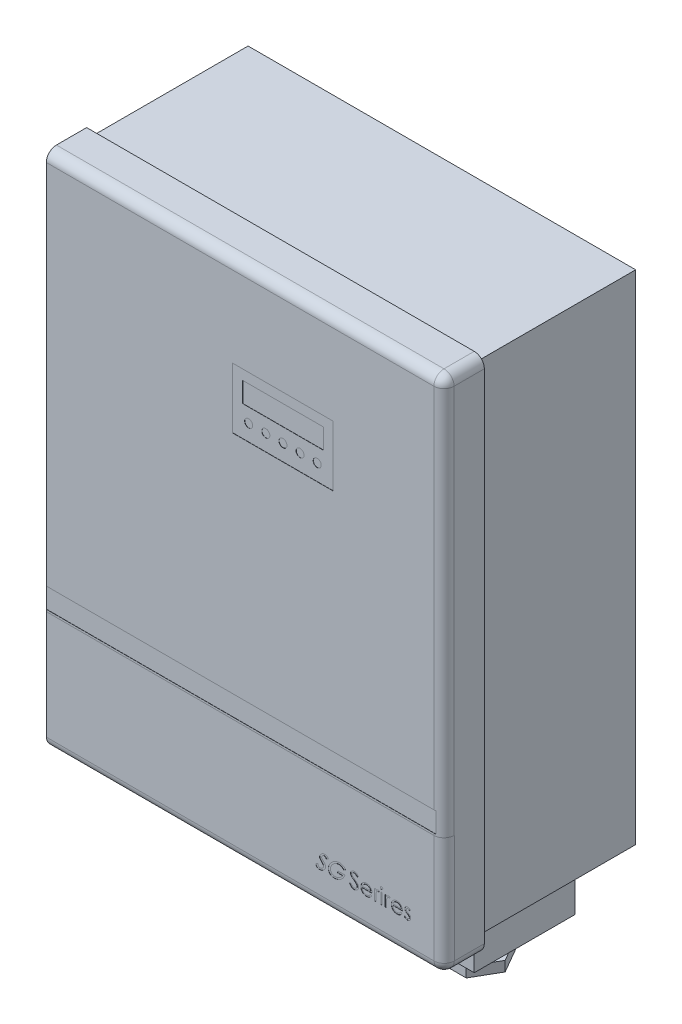
SolidWorks part; units mm, degrees
ref_plane "Alzado" through (0, 0, 0) normal (0, 0, 1) x (1, 0, 0)
ref_plane "Planta" through (0, 0, 0) normal (0, 1, 0) x (1, 0, 0)
ref_plane "Vista lateral" through (0, 0, 0) normal (1, 0, 0) x (0, 0, -1)
sketch "Croquis1" plane through (0, 0, 0) normal (0, 0, 1) x (1, 0, 0)
  line L1 (-323.85, 313.69) -> (323.85, 313.69)
  line L2 (-323.85, 313.69) -> (-323.85, -313.69)
  line L3 (-323.85, -313.69) -> (323.85, -313.69)
  line L4 (323.85, 313.69) -> (323.85, -313.69)
  line L5 (-323.85, 313.69) -> (323.85, -313.69) construction
  line L6 (-323.85, -313.69) -> (323.85, 313.69) construction
  line L7 (-311.15, -300.99) -> (311.15, -300.99)
  line L8 (-311.15, -300.99) -> (-311.15, 300.99)
  line L9 (-311.15, 300.99) -> (311.15, 300.99)
  line L10 (311.15, -300.99) -> (311.15, 300.99)
  line L11 (-311.15, -300.99) -> (311.15, 300.99) construction
  line L12 (-311.15, 300.99) -> (311.15, -300.99) construction
  point P0 (0, 0)
  point P6 (0, 0)
  point P11 (-311.15, 300.99)
  dimension "D1" = 647.7
  dimension "D2" = 627.38
  dimension "D3" = 12.7
  dimension "D4" = 12.7
extrude "Saliente-Extruir1" add sketch "Croquis1" along normal blind 203.2
sketch "Croquis2" plane through (0, 0, 203.2) normal (0, 0, 1) x (1, 0, 0)
  line L0 (323.85, -313.69) -> (323.85, 313.69) construction
  line L1 (-336.55, -326.39) -> (336.55, -326.39)
  line L2 (-336.55, -326.39) -> (-336.55, 326.39)
  line L3 (-336.55, 326.39) -> (336.55, 326.39)
  line L4 (336.55, -326.39) -> (336.55, 326.39)
  line L5 (-336.55, -326.39) -> (336.55, 326.39) construction
  line L6 (-336.55, 326.39) -> (336.55, -326.39) construction
  line L7 (323.85, 313.69) -> (-323.85, 313.69) construction
  point P0 (0, 0)
  dimension "D1" = 12.7
  dimension "D2" = 12.7
extrude "Saliente-Extruir2" add sketch "Croquis2" along normal blind 50.8
sketch "Croquis3" plane through (0, 0, 254) normal (0, 0, 1) x (1, 0, 0)
  line L0 (336.55, -326.39) -> (336.55, 326.39) construction
  line L1 (-336.55, -148.59) -> (336.55, -148.59)
  line L2 (-336.55, -148.59) -> (-336.55, -173.99)
  line L3 (-336.55, -173.99) -> (336.55, -173.99)
  line L4 (336.55, -148.59) -> (336.55, -173.99)
  line L5 (-336.55, -148.59) -> (336.55, -173.99) construction
  line L6 (-336.55, -173.99) -> (336.55, -148.59) construction
  point P0 (336.55, -161.29)
  dimension "D1" = 25.4
  dimension "D2" = 673.1
  dimension "D3" = 165.1
extrude "Cortar-Extruir1" cut sketch "Croquis3" against normal blind 0.254
sketch "Croquis5" plane through (0, 0, 254) normal (0, 0, 1) x (1, 0, 0)
  line L0 (-336.55, -173.99) -> (-336.55, -326.39) construction
  line L1 (-336.55, -176.53) -> (336.55, -176.53)
  line L2 (-336.55, -176.53) -> (-336.55, -326.39)
  line L3 (-336.55, -326.39) -> (336.55, -326.39)
  line L4 (336.55, -176.53) -> (336.55, -326.39)
  line L5 (-336.55, -173.99) -> (336.55, -173.99) construction
  dimension "D1" = 2.54
extrude "Cortar-Extruir2" cut sketch "Croquis5" against normal blind 0.254
fillet "Redondeo1" radius 12.7 4 edges at (336.55, 326.39, 228.6) (336.55, -326.39, 228.473) (-336.55, -326.39, 228.473) (-336.55, 326.39, 228.6)
fillet "Redondeo4" radius 12.7 5 edges at (-336.55, -245.11, 253.746) (-332.8303, -322.6703, 253.746) (336.55, -245.11, 253.746) (332.8303, -322.6703, 253.746) (0, -326.39, 253.746)
fillet "Redondeo5" radius 12.7 5 edges at (336.55, 82.55, 254) (332.8303, 322.6703, 254) (0, 326.39, 254) (-332.8303, 322.6703, 254) (-336.55, 82.55, 254)
sketch "Croquis6" plane through (0, 0, 254) normal (0, 0, 1) x (1, 0, 0)
  line L0 (323.85, -148.59) -> (323.85, 313.69) construction
  line L1 (69.85, 212.09) -> (196.85, 212.09)
  line L2 (69.85, 212.09) -> (69.85, 135.89)
  line L3 (69.85, 135.89) -> (196.85, 135.89)
  line L4 (196.85, 212.09) -> (196.85, 135.89)
  line L5 (323.85, 313.69) -> (-323.85, 313.69) construction
  dimension "D1" = 76.2
  dimension "D2" = 127
  dimension "D3" = 127
  dimension "D4" = 101.6
extrude "Cortar-Extruir3" cut sketch "Croquis6" against normal blind 0.254
sketch "Croquis7" plane through (0, 0, 253.746) normal (0, 0, 1) x (1, 0, 0)
  line L0 (196.85, 212.09) -> (69.85, 212.09) construction
  line L1 (82.55, 173.99) -> (184.15, 173.99)
  line L2 (82.55, 173.99) -> (82.55, 199.39)
  line L3 (82.55, 199.39) -> (184.15, 199.39)
  line L4 (184.15, 173.99) -> (184.15, 199.39)
  line L5 (82.55, 173.99) -> (184.15, 199.39) construction
  line L6 (82.55, 199.39) -> (184.15, 173.99) construction
  line L7 (196.85, 135.89) -> (196.85, 212.09) construction
  line L8 (69.85, 212.09) -> (69.85, 135.89) construction
  point P0 (133.35, 186.69)
  dimension "D1" = 12.7
  dimension "D2" = 12.7
  dimension "D3" = 12.7
  dimension "D4" = 25.4
extrude "Cortar-Extruir4" cut sketch "Croquis7" against normal blind 0.254
sketch "Croquis8" plane through (0, 0, 253.746) normal (0, 0, 1) x (1, 0, 0)
  line L0 (69.85, 135.89) -> (196.85, 135.89) construction
  line L1 (69.85, 212.09) -> (69.85, 135.89) construction
  line L2 (196.85, 135.89) -> (196.85, 212.09) construction
  circle A0 centre (90.17, 156.21) radius 5.08
  circle A1 centre (111.76, 156.21) radius 5.08
  circle A2 centre (133.35, 156.21) radius 5.08
  circle A3 centre (154.94, 156.21) radius 5.08
  circle A4 centre (176.53, 156.21) radius 5.08
  dimension "D1" = 10.16
  dimension "D5" = 20.32
  dimension "D2" = 20.32
  dimension "D3" = 20.32
  dimension "D4" = 5
extrude "Cortar-Extruir5" cut sketch "Croquis8" against normal blind 0.254
sketch "Croquis9" plane through (0, -313.69, 0) normal (0, -1, 0) x (1, 0, 0)
  line L0 (-323.85, 203.2) -> (-323.85, 0) construction
  line L1 (-323.85, 0) -> (323.85, 0) construction
  circle A0 centre (-260.35, 114.3) radius 38.1
  dimension "D1" = 76.2
  dimension "D2" = 63.5
  dimension "D3" = 114.3
extrude "Saliente-Extruir3" add sketch "Croquis9" along normal blind 12.7
sketch "Croquis10" plane through (0, -326.39, 0) normal (0, -1, 0) x (1, 0, 0)
  line L2 (-287.0835, 117.869) -> (-264.795, 126.1967)
  line L3 (-287.0835, 110.731) -> (-264.795, 102.4033)
  line L4 (-255.905, 126.1967) -> (-233.6165, 117.869)
  line L5 (-255.905, 102.4033) -> (-233.6165, 110.731)
  arc A0 (-287.0835, 117.869) -> (-287.0835, 110.731) centre (-285.75, 114.3) ccw
  arc A1 (-233.6165, 110.731) -> (-233.6165, 117.869) centre (-234.95, 114.3) ccw
  arc A2 (-264.795, 102.4033) -> (-255.905, 102.4033) centre (-260.35, 114.3) ccw
  arc A3 (-255.905, 126.1967) -> (-264.795, 126.1967) centre (-260.35, 114.3) ccw
  dimension "D1" = 7.62
  dimension "D2" = 7.62
  dimension "D5" = 25.4
extrude "Saliente-Extruir4" add sketch "Croquis10" along normal blind 25.4
sketch "Croquis11" plane through (0, -313.69, 0) normal (0, -1, 0) x (1, 0, 0)
  line L0 (-38.0669, 140.6157) -> (-38.0669, 149.86)
  line L1 (-38.0669, 129.54) -> (-33.02, 129.54)
  line L2 (-38.0669, 129.54) -> (-38.0669, 138.7843)
  line L3 (-38.0669, 149.86) -> (-33.02, 149.86)
  line L4 (-17.7469, 129.54) -> (-17.7469, 129.5649)
  line L5 (-17.7469, 149.8351) -> (-17.7469, 149.86)
  line L8 (-17.78, 149.86) -> (-17.7469, 149.86)
  line L9 (-17.78, 129.54) -> (-17.7469, 129.54)
  line L10 (0.0331, 129.54) -> (5.08, 129.54)
  line L11 (20.32, 129.54) -> (20.3531, 129.54)
  line L12 (20.3531, 129.54) -> (20.3531, 129.5649)
  line L13 (20.3531, 149.8351) -> (20.3531, 149.86)
  line L14 (20.32, 149.86) -> (20.3531, 149.86)
  line L15 (0.0331, 149.86) -> (5.08, 149.86)
  line L16 (0.0331, 140.6157) -> (0.0331, 149.86)
  line L17 (0.0331, 129.54) -> (0.0331, 138.7843)
  line L18 (0.0331, 91.44) -> (5.08, 91.44)
  line L19 (20.32, 91.44) -> (20.3531, 91.44)
  line L20 (20.3531, 91.44) -> (20.3531, 91.4649)
  line L21 (20.3531, 111.7351) -> (20.3531, 111.76)
  line L22 (20.32, 111.76) -> (20.3531, 111.76)
  line L23 (0.0331, 111.76) -> (5.08, 111.76)
  line L24 (0.0331, 102.5157) -> (0.0331, 111.76)
  line L25 (0.0331, 91.44) -> (0.0331, 100.6843)
  line L26 (0.0331, 53.34) -> (5.08, 53.34)
  line L27 (20.32, 53.34) -> (20.3531, 53.34)
  line L28 (20.3531, 53.34) -> (20.3531, 53.3649)
  line L29 (20.3531, 73.6351) -> (20.3531, 73.66)
  line L30 (20.32, 73.66) -> (20.3531, 73.66)
  line L31 (0.0331, 73.66) -> (5.08, 73.66)
  line L32 (0.0331, 64.4157) -> (0.0331, 73.66)
  line L33 (0.0331, 53.34) -> (0.0331, 62.5843)
  line L34 (-38.0669, 91.44) -> (-33.02, 91.44)
  line L35 (-17.78, 91.44) -> (-17.7469, 91.44)
  line L36 (-17.7469, 91.44) -> (-17.7469, 91.4649)
  line L37 (-17.7469, 111.7351) -> (-17.7469, 111.76)
  line L38 (-17.78, 111.76) -> (-17.7469, 111.76)
  line L39 (-38.0669, 111.76) -> (-33.02, 111.76)
  line L40 (-38.0669, 102.5157) -> (-38.0669, 111.76)
  line L41 (-38.0669, 91.44) -> (-38.0669, 100.6843)
  line L42 (-38.0669, 53.34) -> (-33.02, 53.34)
  line L43 (-17.78, 53.34) -> (-17.7469, 53.34)
  line L44 (-17.7469, 53.34) -> (-17.7469, 53.3649)
  line L45 (-17.7469, 73.6351) -> (-17.7469, 73.66)
  line L46 (-17.78, 73.66) -> (-17.7469, 73.66)
  line L47 (-38.0669, 73.66) -> (-33.02, 73.66)
  line L48 (-38.0669, 64.4157) -> (-38.0669, 73.66)
  line L49 (-38.0669, 53.34) -> (-38.0669, 62.5843)
  line L50 (-323.85, 203.2) -> (323.85, 203.2) construction
  line L51 (-323.85, 0) -> (323.85, 0) construction
  line L52 (-323.85, 203.2) -> (-323.85, 0) construction
  arc A0 (-38.0669, 140.6157) -> (-38.0669, 138.7843) centre (-25.4, 139.7) ccw
  arc A1 (-33.02, 129.54) -> (-17.78, 129.54) centre (-25.4, 139.7) ccw
  arc A2 (-17.7469, 129.5649) -> (-17.7469, 149.8351) centre (-25.4, 139.7) ccw
  arc A3 (-17.78, 149.86) -> (-33.02, 149.86) centre (-25.4, 139.7) ccw
  arc A4 (5.08, 129.54) -> (20.32, 129.54) centre (12.7, 139.7) ccw
  arc A5 (20.3531, 129.5649) -> (20.3531, 149.8351) centre (12.7, 139.7) ccw
  arc A6 (20.32, 149.86) -> (5.08, 149.86) centre (12.7, 139.7) ccw
  arc A7 (0.0331, 140.6157) -> (0.0331, 138.7843) centre (12.7, 139.7) ccw
  arc A8 (5.08, 91.44) -> (20.32, 91.44) centre (12.7, 101.6) ccw
  arc A9 (20.3531, 91.4649) -> (20.3531, 111.7351) centre (12.7, 101.6) ccw
  arc A10 (20.32, 111.76) -> (5.08, 111.76) centre (12.7, 101.6) ccw
  arc A11 (0.0331, 102.5157) -> (0.0331, 100.6843) centre (12.7, 101.6) ccw
  arc A12 (5.08, 53.34) -> (20.32, 53.34) centre (12.7, 63.5) ccw
  arc A13 (20.3531, 53.3649) -> (20.3531, 73.6351) centre (12.7, 63.5) ccw
  arc A14 (20.32, 73.66) -> (5.08, 73.66) centre (12.7, 63.5) ccw
  arc A15 (0.0331, 64.4157) -> (0.0331, 62.5843) centre (12.7, 63.5) ccw
  arc A16 (-33.02, 91.44) -> (-17.78, 91.44) centre (-25.4, 101.6) ccw
  arc A17 (-17.7469, 91.4649) -> (-17.7469, 111.7351) centre (-25.4, 101.6) ccw
  arc A18 (-17.78, 111.76) -> (-33.02, 111.76) centre (-25.4, 101.6) ccw
  arc A19 (-38.0669, 102.5157) -> (-38.0669, 100.6843) centre (-25.4, 101.6) ccw
  arc A20 (-33.02, 53.34) -> (-17.78, 53.34) centre (-25.4, 63.5) ccw
  arc A21 (-17.7469, 53.3649) -> (-17.7469, 73.6351) centre (-25.4, 63.5) ccw
  arc A22 (-17.78, 73.66) -> (-33.02, 73.66) centre (-25.4, 63.5) ccw
  arc A23 (-38.0669, 64.4157) -> (-38.0669, 62.5843) centre (-25.4, 63.5) ccw
  dimension "D1" = 25.4
  dimension "D2" = 20.32
  dimension "D3" = 20.32
  dimension "D6" = 63.5
  dimension "D7" = 63.5
  dimension "D8" = 203.2
  dimension "D4" = 2
  dimension "D5" = 3
extrude "Saliente-Extruir5" add sketch "Croquis11" along normal blind 50.8
sketch "Croquis12" plane through (0, -313.69, 0) normal (0, -1, 0) x (-1, 0, 0)
  line L0 (323.85, -203.2) -> (-323.85, -203.2) construction
  line L1 (323.85, -203.2) -> (323.85, 0) construction
  line L2 (-64.5291, -127.001) -> (-76.044, -127.001)
  line L3 (-64.5291, -127.001) -> (-64.5291, -134.692)
  line L4 (-64.5291, -147.321) -> (-66.0407, -147.321)
  line L5 (-84.8491, -127.001) -> (-84.8491, -130.4004)
  line L6 (-102.6291, -144.708) -> (-102.6291, -147.321)
  line L8 (-64.5291, -144.708) -> (-64.5291, -147.321)
  line L9 (-86.3593, -147.321) -> (-84.8491, -147.321)
  line L10 (-84.8491, -148.9996) -> (-84.8491, -147.321)
  line L11 (-76.356, -127.001) -> (-84.8491, -127.001)
  line L12 (-102.6291, -147.321) -> (-104.1407, -147.321)
  line L13 (-124.4593, -147.321) -> (-122.9491, -147.321)
  line L14 (-122.9491, -148.9996) -> (-122.9491, -147.321)
  line L15 (-122.9491, -127.001) -> (-122.9491, -130.4004)
  line L16 (-114.456, -127.001) -> (-122.9491, -127.001)
  line L17 (-102.6291, -127.001) -> (-114.144, -127.001)
  line L18 (-102.6291, -127.001) -> (-102.6291, -134.692)
  line L19 (-102.6291, -106.608) -> (-102.6291, -109.221)
  line L20 (-102.6291, -109.221) -> (-104.1407, -109.221)
  line L21 (-124.4593, -109.221) -> (-122.9491, -109.221)
  line L22 (-122.9491, -110.8996) -> (-122.9491, -109.221)
  line L23 (-122.9491, -88.901) -> (-122.9491, -92.3004)
  line L24 (-114.456, -88.901) -> (-122.9491, -88.901)
  line L25 (-102.6291, -88.901) -> (-114.144, -88.901)
  line L26 (-102.6291, -88.901) -> (-102.6291, -96.592)
  line L27 (-102.6291, -68.508) -> (-102.6291, -71.121)
  line L28 (-102.6291, -71.121) -> (-104.1407, -71.121)
  line L29 (-124.4593, -71.121) -> (-122.9491, -71.121)
  line L30 (-122.9491, -72.7996) -> (-122.9491, -71.121)
  line L31 (-122.9491, -50.801) -> (-122.9491, -54.2004)
  line L32 (-114.456, -50.801) -> (-122.9491, -50.801)
  line L33 (-102.6291, -50.801) -> (-114.144, -50.801)
  line L34 (-102.6291, -50.801) -> (-102.6291, -58.492)
  line L35 (-64.5291, -106.608) -> (-64.5291, -109.221)
  line L36 (-64.5291, -109.221) -> (-66.0407, -109.221)
  line L37 (-86.3593, -109.221) -> (-84.8491, -109.221)
  line L38 (-84.8491, -110.8996) -> (-84.8491, -109.221)
  line L39 (-84.8491, -88.901) -> (-84.8491, -92.3004)
  line L40 (-76.356, -88.901) -> (-84.8491, -88.901)
  line L41 (-64.5291, -88.901) -> (-76.044, -88.901)
  line L42 (-64.5291, -88.901) -> (-64.5291, -96.592)
  line L43 (-64.5291, -68.508) -> (-64.5291, -71.121)
  line L44 (-64.5291, -71.121) -> (-66.0407, -71.121)
  line L45 (-86.3593, -71.121) -> (-84.8491, -71.121)
  line L46 (-84.8491, -72.7996) -> (-84.8491, -71.121)
  line L47 (-84.8491, -50.801) -> (-84.8491, -54.2004)
  line L48 (-76.356, -50.801) -> (-84.8491, -50.801)
  line L49 (-64.5291, -50.801) -> (-76.044, -50.801)
  line L50 (-64.5291, -50.801) -> (-64.5291, -58.492)
  arc A0 (-64.5291, -144.708) -> (-64.5291, -134.692) centre (-76.2, -139.7) ccw
  arc A1 (-86.3593, -147.321) -> (-66.0407, -147.321) centre (-76.2, -139.7) ccw
  arc A2 (-76.044, -127.001) -> (-76.356, -127.001) centre (-76.2, -139.7) ccw
  arc A3 (-84.8491, -130.4004) -> (-84.8491, -148.9996) centre (-76.2, -139.7) ccw
  arc A4 (-124.4593, -147.321) -> (-104.1407, -147.321) centre (-114.3, -139.7) ccw
  arc A5 (-122.9491, -130.4004) -> (-122.9491, -148.9996) centre (-114.3, -139.7) ccw
  arc A6 (-114.144, -127.001) -> (-114.456, -127.001) centre (-114.3, -139.7) ccw
  arc A7 (-102.6291, -144.708) -> (-102.6291, -134.692) centre (-114.3, -139.7) ccw
  arc A8 (-124.4593, -109.221) -> (-104.1407, -109.221) centre (-114.3, -101.6) ccw
  arc A9 (-122.9491, -92.3004) -> (-122.9491, -110.8996) centre (-114.3, -101.6) ccw
  arc A10 (-114.144, -88.901) -> (-114.456, -88.901) centre (-114.3, -101.6) ccw
  arc A11 (-102.6291, -106.608) -> (-102.6291, -96.592) centre (-114.3, -101.6) ccw
  arc A12 (-124.4593, -71.121) -> (-104.1407, -71.121) centre (-114.3, -63.5) ccw
  arc A13 (-122.9491, -54.2004) -> (-122.9491, -72.7996) centre (-114.3, -63.5) ccw
  arc A14 (-114.144, -50.801) -> (-114.456, -50.801) centre (-114.3, -63.5) ccw
  arc A15 (-102.6291, -68.508) -> (-102.6291, -58.492) centre (-114.3, -63.5) ccw
  arc A16 (-86.3593, -109.221) -> (-66.0407, -109.221) centre (-76.2, -101.6) ccw
  arc A17 (-84.8491, -92.3004) -> (-84.8491, -110.8996) centre (-76.2, -101.6) ccw
  arc A18 (-76.044, -88.901) -> (-76.356, -88.901) centre (-76.2, -101.6) ccw
  arc A19 (-64.5291, -106.608) -> (-64.5291, -96.592) centre (-76.2, -101.6) ccw
  arc A20 (-86.3593, -71.121) -> (-66.0407, -71.121) centre (-76.2, -63.5) ccw
  arc A21 (-84.8491, -54.2004) -> (-84.8491, -72.7996) centre (-76.2, -63.5) ccw
  arc A22 (-76.044, -50.801) -> (-76.356, -50.801) centre (-76.2, -63.5) ccw
  arc A23 (-64.5291, -68.508) -> (-64.5291, -58.492) centre (-76.2, -63.5) ccw
  dimension "D1" = 25.4
  dimension "D2" = 63.5
  dimension "D3" = 20.32
  dimension "D4" = 20.32
  dimension "D5" = 304.8
  dimension "D6" = 2
  dimension "D7" = 3
extrude "Saliente-Extruir7" add sketch "Croquis12" along normal blind 38.1 rebuild error yes
sketch "Croquis13" plane through (0, -313.69, 0) normal (0, -1, 0) x (1, 0, 0)
  line L0 (-323.85, 203.2) -> (323.85, 203.2) construction
  line L1 (90.4291, 165.1) -> (285.75, 165.1)
  line L2 (90.4291, 165.1) -> (90.4291, 38.1)
  line L3 (90.4291, 38.1) -> (285.75, 38.1)
  line L4 (285.75, 165.1) -> (285.75, 38.1)
  line L5 (-323.85, 0) -> (323.85, 0) construction
  line L6 (323.85, 203.2) -> (323.85, 0) construction
  dimension "D1" = 38.1
  dimension "D2" = 38.1
  dimension "D3" = 38.1
extrude "Saliente-Extruir8" add sketch "Croquis13" along normal blind 76.2
sketch "Croquis14" plane through (0, -389.89, 0) normal (0, -1, 0) x (1, 0, 0)
  line L0 (285.75, 165.1) -> (90.4291, 165.1) construction
  line L1 (90.4291, 165.1) -> (164.8775, 165.1)
  line L2 (90.4291, 165.1) -> (90.4291, 38.1)
  line L3 (90.4291, 38.1) -> (164.8775, 38.1)
  line L4 (164.8775, 165.1) -> (164.8775, 38.1)
  line L5 (90.4291, 165.1) -> (90.4291, 38.1) construction
  line L6 (90.4291, 38.1) -> (285.75, 38.1) construction
extrude "Cortar-Extruir6" cut sketch "Croquis14" against normal blind 25.4
fillet "Redondeo9" radius 25.4 1 edges at (164.8775, -364.49, 101.6)
sketch "Croquis15" plane through (0, -389.89, 0) normal (0, -1, 0) x (1, 0, 0)
  line L0 (285.75, 165.1) -> (164.8775, 165.1) construction
  line L1 (261.2139, 101.6) -> (243.2559, 132.7041)
  line L2 (243.2559, 132.7041) -> (207.3401, 132.7041)
  line L3 (207.3401, 132.7041) -> (189.3821, 101.6)
  line L4 (189.3821, 101.6) -> (207.3401, 70.4959)
  line L5 (207.3401, 70.4959) -> (243.2559, 70.4959)
  line L6 (243.2559, 70.4959) -> (261.2139, 101.6)
  line L9 (285.75, 38.1) -> (285.75, 165.1) construction
  circle A0 centre (225.298, 101.6) radius 31.1041 construction
  dimension "D1" = 63.5
  dimension "D2" = 60.452
extrude "Saliente-Extruir9" add sketch "Croquis15" along normal blind 5.08
sketch "Croquis16" plane through (0, -394.97, 0) normal (0, -1, 0) x (1, 0, 0)
  circle A0 centre (225.298, 101.6) radius 25.4
  dimension "D1" = 50.8
extrude "Saliente-Extruir10" add sketch "Croquis16" along normal blind 25.4
sketch "Croquis17" plane through (0, -420.37, 0) normal (0, -1, 0) x (1, 0, 0)
  line L1 (261.2139, 101.6) -> (243.2559, 132.7041)
  line L2 (243.2559, 132.7041) -> (207.3401, 132.7041)
  line L3 (207.3401, 132.7041) -> (189.3821, 101.6)
  line L4 (189.3821, 101.6) -> (207.3401, 70.4959)
  line L5 (207.3401, 70.4959) -> (243.2559, 70.4959)
  line L6 (243.2559, 70.4959) -> (261.2139, 101.6)
  circle A0 centre (225.298, 101.6) radius 31.1041 construction
extrude "Saliente-Extruir11" add sketch "Croquis17" along normal blind 12.7
sketch "Croquis18" plane through (0, -433.07, 0) normal (0, -1, 0) x (1, 0, 0)
  circle A0 centre (225.298, 101.6) radius 19.05
  dimension "D1" = 38.1
extrude "Cortar-Extruir7" cut sketch "Croquis18" against normal blind 177.8
sketch "Croquis19" plane through (0, 0, 253.746) normal (0, 0, 1) x (1, 0, 0)
  line L0 (-294.5564, -278.5126) -> (-70.5709, -278.5126) construction
  line L1 (195.5649, -278.5126) -> (295.8425, -278.5126) construction
  text T0 "Solis" font "Century Gothic" height in points 72
extrude "Cortar-Extruir8" cut sketch "Croquis19" against normal blind 0.254
sketch "Croquis20" plane through (0, 0, 253.746) normal (0, 0, 1) x (1, 0, 0)
  line L0 (172.9436, -285.6351) -> (302.3962, -285.6351) construction
  text T0 "<b><i>SG</i></b> Serires" font "Century Gothic" height in points 72
extrude "Cortar-Extruir9" cut sketch "Croquis20" against normal blind 0.254
sketch "Croquis21" plane through (0, 0, 0) normal (0, 0, -1) x (-1, 0, 0)
  line L1 (-323.85, 313.69) -> (323.85, 313.69)
  line L2 (-323.85, 313.69) -> (-323.85, -313.69)
  line L3 (-323.85, -313.69) -> (323.85, -313.69)
  line L4 (323.85, 313.69) -> (323.85, -313.69)
extrude "Saliente-Extruir12" add sketch "Croquis21" along normal blind 0.254
sketch "Croquis22" plane through (-336.55, 0, 0) normal (-1, 0, 0) x (0, 0, 1)
  line L1 (-67.1503, 343.6952) -> (297.187, 343.6952)
  line L2 (-67.1503, 343.6952) -> (-67.1503, -411.4788)
  line L3 (-67.1503, -411.4788) -> (297.187, -411.4788)
  line L4 (297.187, 343.6952) -> (297.187, -411.4788)
  point P4 (297.187, -411.4788)
extrude "Cortar-Extruir10" cut sketch "Croquis22" against normal blind 171.958
